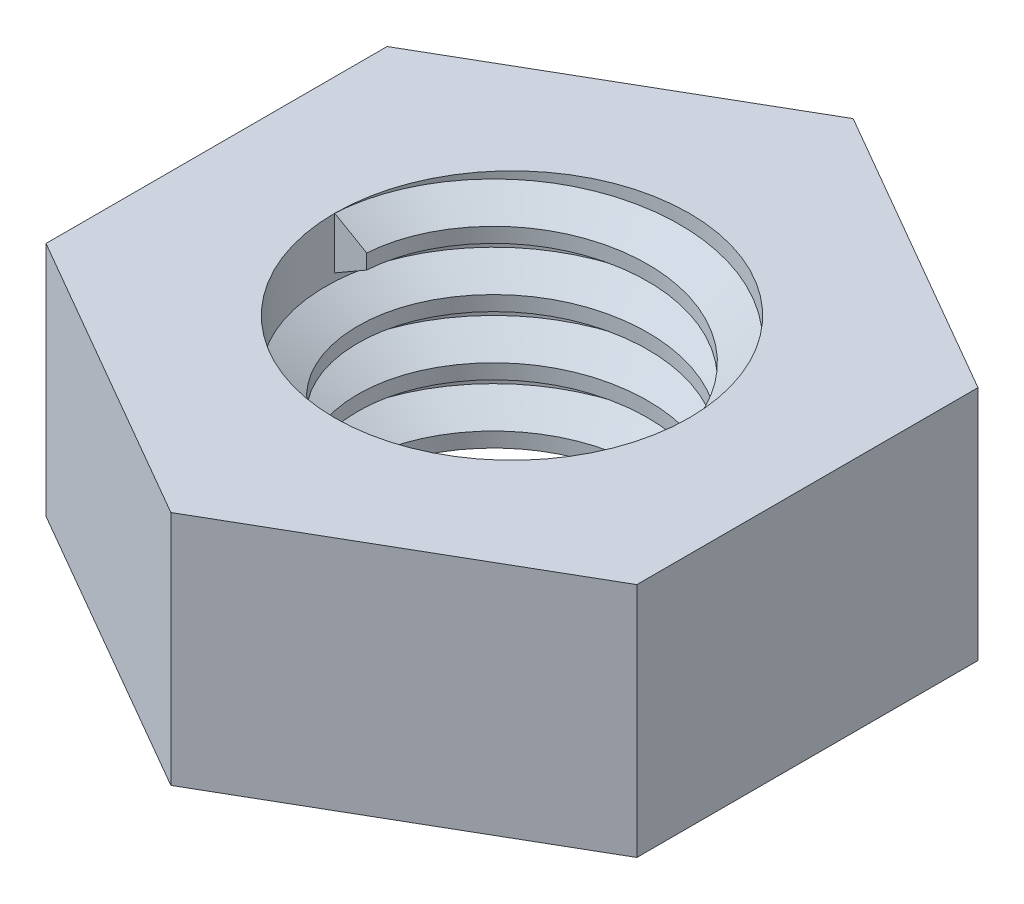
SolidWorks part; units mm, degrees
material "Alloy Steel"
ref_plane "Front Plane" through (0, 0, 0) normal (0, 0, 1) x (1, 0, 0)
ref_plane "Top Plane" through (0, 0, 0) normal (0, 1, 0) x (1, 0, 0)
ref_plane "Right Plane" through (0, 0, 0) normal (1, 0, 0) x (0, 0, -1)
sketch "Sketch1" plane through (0, 0, 0) normal (0, 1, 0) x (1, 0, 0)
  line L1 (7.9375, -4.5827) -> (7.9375, 4.5827)
  line L2 (7.9375, 4.5827) -> (0, 9.1654)
  line L3 (0, 9.1654) -> (-7.9375, 4.5827)
  line L4 (-7.9375, 4.5827) -> (-7.9375, -4.5827)
  line L5 (-7.9375, -4.5827) -> (0, -9.1654)
  line L6 (0, -9.1654) -> (7.9375, -4.5827)
  circle A0 centre (0, 0) radius 7.9375 construction
  point P1 (0, 0)
  dimension "D1" = 15.875
extrude "Boss-Extrude1" add sketch "Sketch1" along normal blind 6.35
sketch "Sketch2" plane through (0, 6.35, 0) normal (0, 1, 0) x (1, 0, 0)
  circle A0 centre (0, 0) radius 4.7625
  dimension "D1" = 9.525
extrude "Cut-Extrude1" cut sketch "Sketch2" against normal through all
thread "Thread1" pitch 1.5875 method extrude profile "Thread Profile1" start angle 0, offset 0, length 0, pitch 1.5875, diameter 9.525
ref_plane "Plane1" through (-4.7625, 6.35, 0) normal (0, 0, 1) x (-1, 0, 0)
sketch "Thread Profile1" plane through (-4.7625, 6.35, 0) normal (0, 0, 1) x (-1, 0, 0)
  line L0 (0, 0) -> (0, 1.5875) construction
  line L11 (0, 0) -> (0, 1.3891)
  line L12 (0, 1.3891) -> (-0.8593, 0.893)
  line L13 (-0.8593, 0.893) -> (-0.8593, 0.4961)
  line L15 (-0.8593, 0.4961) -> (0, 0)
  line L17 (-0.8593, 0.6945) -> (0, 0.6945) construction
  point P2 (0, 0)
  dimension "Pitch" = 1.5875
  dimension "Profile_Angle" = 60
  dimension "Profile_Land" = 0.3969
  dimension "Profile_Height" = 0.8593
